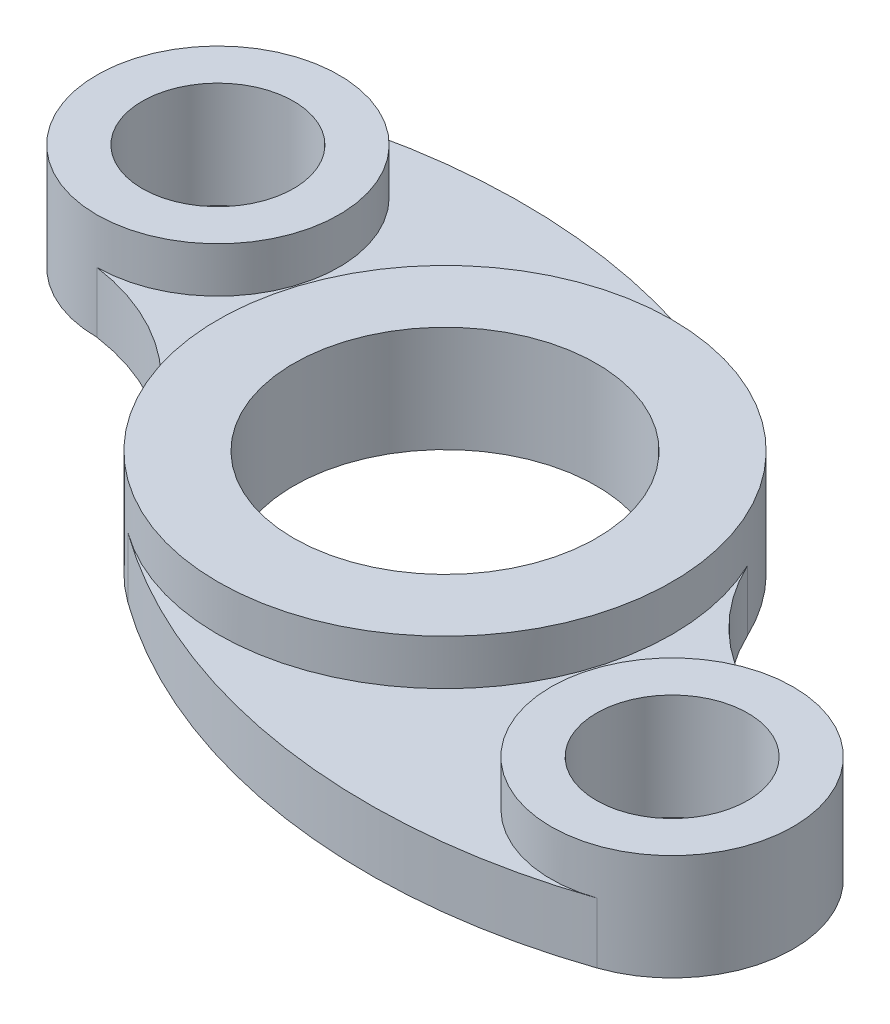
SolidWorks part; units mm, degrees
ref_plane "Piano frontale" through (0, 0, 0) normal (0, 0, 1) x (1, 0, 0)
ref_plane "Piano superiore" through (0, 0, 0) normal (0, 1, 0) x (1, 0, 0)
ref_plane "Piano destro" through (0, 0, 0) normal (1, 0, 0) x (0, 0, -1)
sketch "Schizzo1" plane through (0, 0, 0) normal (0, 1, 0) x (1, 0, 0)
  line L0 (0, 66.3771) -> (0, -66.3771) construction
  line L1 (-99.6482, 0) -> (99.6482, 0) construction
  circle A0 centre (0, 0) radius 30
  circle A1 centre (0, 0) radius 20
  circle A2 centre (50, -20) radius 16
  circle A3 centre (50, -20) radius 10
  circle A4 centre (-50, 20) radius 16
  circle A5 centre (-50, 20) radius 10
  arc A6 (-55.1854, 35.1364) -> (17.555, 24.3274) centre (-29.2583, -40.5457) cw
  arc A7 (-17.555, -24.3274) -> (55.1854, -35.1364) centre (29.2583, 40.5457) ccw
  arc A8 (27.1081, 12.8511) -> (50, -4) centre (54.2162, 25.7023) ccw
  arc A9 (-50, 4) -> (-27.1081, -12.8511) centre (-54.2162, -25.7023) cw
  point P13 (0, 0)
  point P16 (0, 0)
  point P28 (0, 0)
  point P29 (0, 0)
  dimension "D1" = 60
  dimension "D2" = 40
  dimension "D3" = 32
  dimension "D4" = 20
  dimension "D9" = 80
  dimension "D10" = 30
  dimension "D5" = 20
  dimension "D6" = 20
  dimension "D7" = 100
  dimension "D8" = 50
extrude "Estrusione-Estrusione1" add sketch "Schizzo1" along normal blind 8 contours A4 A9 A0 A6 | A8 A0 A7 A2 region at (26.096, 0, 23.9778) region at (-26.096, 0, -23.9778)
extrude "Estrusione-Estrusione2" add sketch "Schizzo1<8>" along normal blind 14 contours A4 A5 | A0 A1 | A2 A3 region at (13.2765, 0, 25.9527) region at (60.9937, 0, 9.0063) region at (-40.9617, 0, -32.6504)
sketch "Schizzo1<8>" plane through (0, 0, 0) normal (0, 1, 0) x (1, 0, 0) same geometry as "Schizzo1"
